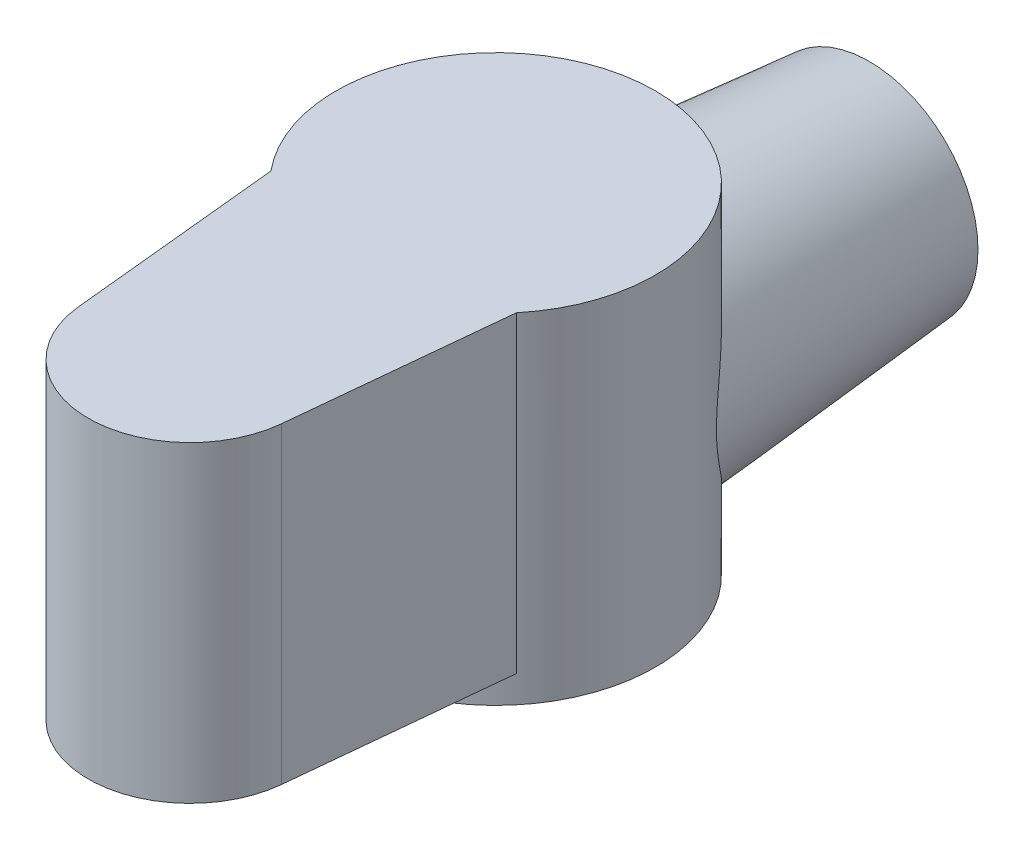
SolidWorks part; units mm, degrees
ref_plane "Front Plane" through (0, 0, 0) normal (0, 0, 1) x (1, 0, 0)
ref_plane "Top Plane" through (0, 0, 0) normal (0, 1, 0) x (1, 0, 0)
ref_plane "Right Plane" through (0, 0, 0) normal (1, 0, 0) x (0, 0, -1)
sketch "Sketch1" plane through (0, 0, 0) normal (0, 1, 0) x (1, 0, 0)
  line L0 (0, 0) -> (0, -45) construction
  line L1 (0, 0) -> (0, 50) construction
  line L11 (0, 50) -> (16, 50)
  line L12 (0, 50) -> (-16, 50)
  line L15 (-18.0727, -15.0209) -> (-14.9256, -46.4926)
  line L16 (18.0727, -15.0209) -> (14.9256, -46.4926)
  line L17 (-16, 50) -> (-19.7217, 12.7791)
  line L18 (16, 50) -> (19.7217, 12.7791)
  circle A0 centre (0, 0) radius 23.5
  arc A1 (-14.9256, -46.4926) -> (14.9256, -46.4926) centre (0, -45) ccw
  dimension "D1" = 47
  dimension "D3" = 32
  dimension "D4" = 5.711
  dimension "D5" = 45
  dimension "D6" = 50
  dimension "D7" = 5.71
extrude "Boss-Extrude1" add sketch "Sketch1" against normal blind 46 contours L15 A1 L16 A0 region at (0, 0, 38.4379)
extrude "Boss-Extrude2" add sketch "Sketch1<3>" against normal blind 50 contours A0
sketch "Sketch1<3>" plane through (0, 0, 0) normal (0, 1, 0) x (1, 0, 0) same geometry as "Sketch1"
ref_plane "Plane1" through (0, -28, 0) normal (0, 1, 0) x (1, 0, 0)
sketch "Sketch2" plane through (0, -28, 0) normal (0, 1, 0) x (1, 0, 0)
  line L0 (-19.7217, 12.7791) -> (0, 12.7791)
  line L1 (0, 0) -> (0, 55) construction
  line L3 (0, 55) -> (-16, 55)
  line L4 (0, 12.7791) -> (0, 55)
  line L6 (-16, 55) -> (-19.7217, 12.7791)
revolve "Revolve1" add sketch "Sketch2" angle 360 about L1
sketch "Sketch5" plane through (0, -46, 0) normal (0, -1, 0) x (-1, 0, 0)
  line L0 (0, -45) -> (0, -60) construction
  arc A0 (-14.9256, -46.4926) -> (14.9256, -46.4926) centre (0, -45) ccw construction
  point P6 (0, 0)
